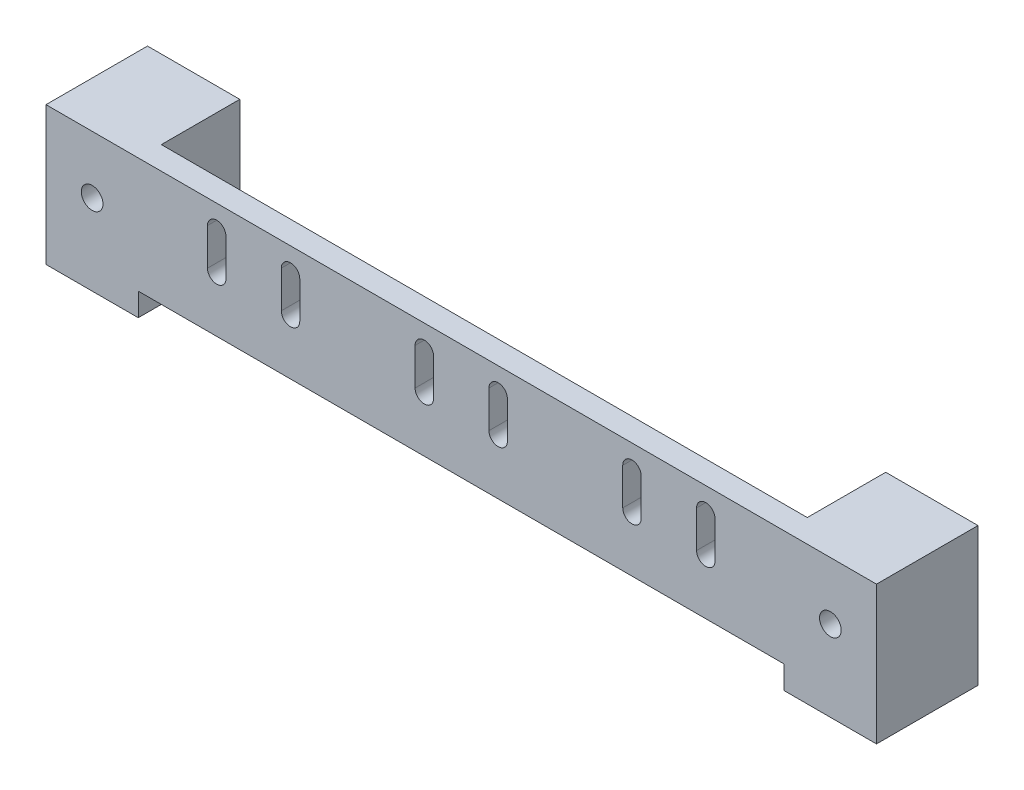
SolidWorks part; units mm, degrees
material "ABS"
ref_plane "Front Plane" through (0, 0, 0) normal (0, 0, 1) x (1, 0, 0)
ref_plane "Top Plane" through (0, 0, 0) normal (0, 1, 0) x (1, 0, 0)
ref_plane "Right Plane" through (0, 0, 0) normal (1, 0, 0) x (0, 0, -1)
sketch "Sketch1" plane through (0, 0, 0) normal (0, 0, 1) x (1, 0, 0)
  line L1 (0, 0) -> (180, 0)
  line L2 (0, 0) -> (0, 30)
  line L3 (0, 30) -> (180, 30)
  line L4 (180, 0) -> (180, 30)
  circle A0 centre (10, 17.5) radius 2.35
  circle A1 centre (170, 17.5) radius 2.35
  dimension "D2" = 4.7
  dimension "D1" = 180
  dimension "D3" = 30
  dimension "D4" = 160
  dimension "D5" = 10
  dimension "D6" = 12.5
extrude "Boss-Extrude1" add sketch "Sketch1" along normal blind 22
sketch "Sketch2" plane through (0, 30, 0) normal (0, 1, 0) x (1, 0, 0)
  line L0 (180, 0) -> (0, 0) construction
  line L1 (160, 0) -> (20, 0)
  line L2 (160, 0) -> (160, -17)
  line L3 (160, -17) -> (20, -17)
  line L4 (20, 0) -> (20, -17)
  line L5 (180, -22) -> (180, 0) construction
  line L6 (0, -22) -> (0, 0) construction
  dimension "D1" = 20
  dimension "D2" = 20
  dimension "D3" = 17
extrude "Cut-Extrude1" cut sketch "Sketch2" against normal blind 30
sketch "Sketch3" plane through (0, 0, 22) normal (0, 0, 1) x (1, 0, 0)
  line L1 (20, 0) -> (160, 0)
  line L2 (20, 0) -> (20, 5)
  line L3 (20, 5) -> (160, 5)
  line L4 (160, 0) -> (160, 5)
  line L5 (0, 30) -> (0, 0) construction
  line L6 (180, 0) -> (180, 30) construction
  line L7 (0, 0) -> (180, 0) construction
  dimension "D1" = 20
  dimension "D2" = 20
  dimension "D3" = 5
extrude "Cut-Extrude2" cut sketch "Sketch3" against normal blind 22
sketch "Sketch4" plane through (0, 0, 22) normal (0, 0, 1) x (1, 0, 0)
  line L3 (143, 16.808) -> (143, 24.808) construction
  line L4 (141, 16.808) -> (141, 24.808)
  line L5 (145, 16.808) -> (145, 24.808)
  line L7 (160, 5) -> (20, 5) construction
  line L8 (180, 0) -> (180, 30) construction
  line L9 (98, 16.808) -> (98, 24.808) construction
  line L10 (96, 16.808) -> (96, 24.808)
  line L11 (100, 16.808) -> (100, 24.808)
  line L12 (53, 16.808) -> (53, 24.808) construction
  line L13 (51, 16.808) -> (51, 24.808)
  line L14 (55, 16.808) -> (55, 24.808)
  line L15 (37, 16.808) -> (37, 24.808) construction
  line L16 (35, 16.808) -> (35, 24.808)
  line L17 (39, 16.808) -> (39, 24.808)
  line L18 (0, 30) -> (0, 0) construction
  line L19 (82, 16.808) -> (82, 24.808) construction
  line L20 (80, 16.808) -> (80, 24.808)
  line L21 (84, 16.808) -> (84, 24.808)
  line L22 (127, 16.808) -> (127, 24.808) construction
  line L23 (125, 16.808) -> (125, 24.808)
  line L24 (129, 16.808) -> (129, 24.808)
  arc A3 (141, 16.808) -> (145, 16.808) centre (143, 16.808) ccw
  arc A4 (145, 24.808) -> (141, 24.808) centre (143, 24.808) ccw
  arc A5 (96, 16.808) -> (100, 16.808) centre (98, 16.808) ccw
  arc A6 (100, 24.808) -> (96, 24.808) centre (98, 24.808) ccw
  arc A7 (51, 16.808) -> (55, 16.808) centre (53, 16.808) ccw
  arc A8 (55, 24.808) -> (51, 24.808) centre (53, 24.808) ccw
  arc A9 (35, 16.808) -> (39, 16.808) centre (37, 16.808) ccw
  arc A10 (39, 24.808) -> (35, 24.808) centre (37, 24.808) ccw
  arc A11 (80, 16.808) -> (84, 16.808) centre (82, 16.808) ccw
  arc A12 (84, 24.808) -> (80, 24.808) centre (82, 24.808) ccw
  arc A13 (125, 16.808) -> (129, 16.808) centre (127, 16.808) ccw
  arc A14 (129, 24.808) -> (125, 24.808) centre (127, 24.808) ccw
  point P7 (143, 20.808)
  point P8 (98, 20.808)
  point P20 (53, 20.808)
  point P27 (37, 20.808)
  point P37 (82, 20.808)
  point P44 (127, 20.808)
  dimension "D1" = 15.808
  dimension "D3" = 4
  dimension "D4" = 8
  dimension "D8" = 8
  dimension "D2" = 37
  dimension "D5" = 3
  dimension "D6" = 45
  dimension "D7" = 37
  dimension "D9" = 4
  dimension "D10" = 15.808
  dimension "D12" = 45
  dimension "D11" = 3
extrude "Cut-Extrude3" cut sketch "Sketch4" against normal blind 48
